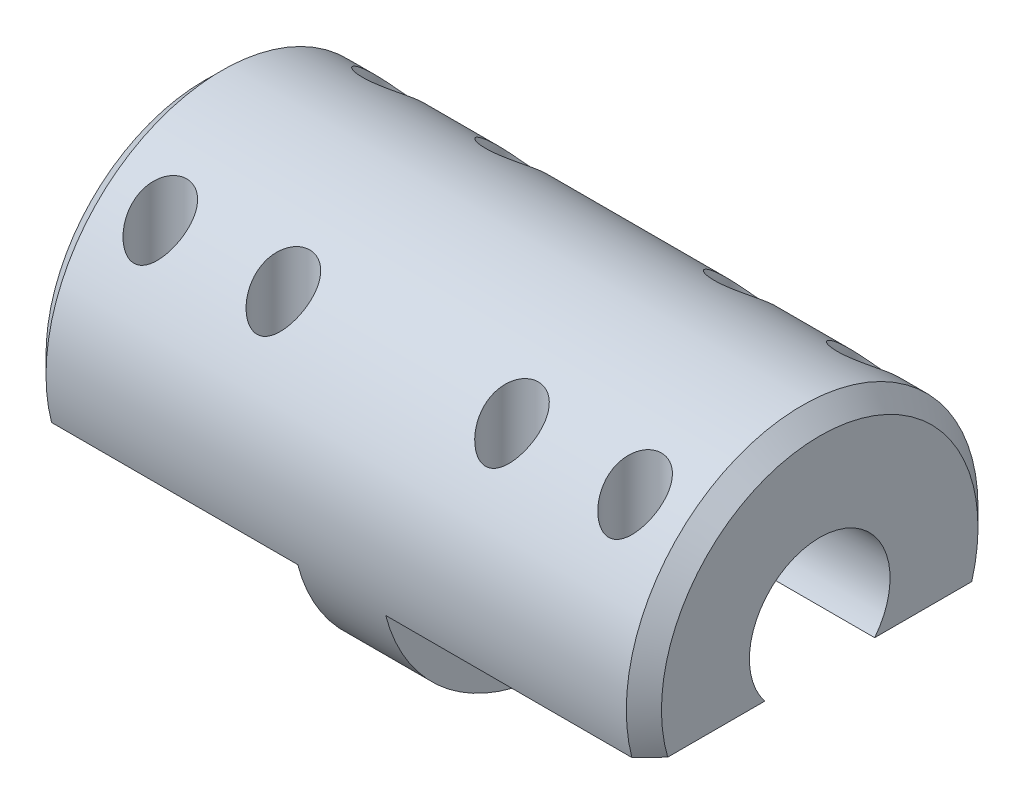
SolidWorks part; units mm, degrees
ref_plane "前视基准面" through (0, 0, 0) normal (0, 0, 1) x (1, 0, 0)
ref_plane "上视基准面" through (0, 0, 0) normal (0, 1, 0) x (1, 0, 0)
ref_plane "右视基准面" through (0, 0, 0) normal (1, 0, 0) x (0, 0, -1)
sketch "草图1" plane through (0, 0, 0) normal (1, 0, 0) x (0, 0, -1)
  circle A0 centre (0, 0) radius 10
  circle A1 centre (0, 0) radius 4
  dimension "D1" = 20
  dimension "D2" = 8
extrude "凸台-拉伸1" add sketch "草图1" along normal blind 35
chamfer "倒角1" distance 1 angle 45 2 edges at (35, 0, -10) (0, 0, -10)
ref_plane "基准面1" through (0, -10, 0) normal (0, -1, 0) x (-1, 0, 0)
sketch "草图3" plane through (0, -10, 0) normal (0, -1, 0) x (-1, 0, 0)
  line L0 (-17.5, 10) -> (-17.5, -10) construction
  line L1 (-1, 10) -> (-34, 10) construction
  line L2 (-34, -10) -> (-1, -10) construction
  line L3 (-7.5, 10) -> (-7.5, 0) construction
  line L4 (-15, 10) -> (0, 10)
  line L5 (-15, 10) -> (-15, -10)
  line L6 (-15, -10) -> (0, -10)
  line L7 (0, 10) -> (0, -10)
  line L8 (-7.5, 0) -> (0, 0) construction
  line L9 (-27.5, 0) -> (-35, 0) construction
  line L10 (-27.5, 10) -> (-27.5, 0) construction
  line L11 (-35, 10) -> (-35, -10)
  line L12 (-20, -10) -> (-35, -10)
  line L13 (-20, 10) -> (-20, -10)
  line L14 (-20, 10) -> (-35, 10)
  circle A0 centre (-4, 6.5) radius 1.5
  circle A1 centre (-11, 6.5) radius 1.5
  circle A2 centre (-11, -6.5) radius 1.5
  circle A3 centre (-4, -6.5) radius 1.5
  circle A4 centre (-31, -6.5) radius 1.5
  circle A5 centre (-24, -6.5) radius 1.5
  circle A6 centre (-24, 6.5) radius 1.5
  circle A7 centre (-31, 6.5) radius 1.5
  dimension "D2" = 3
  dimension "D3" = 4
  dimension "D4" = 13
  dimension "D1" = 15
extrude "切除-拉伸1" cut sketch "草图3" against normal blind 7.5 contours L14 L11 L12 L13 | L4 L7 L6 L5
extrude "切除-拉伸2" cut sketch "草图3<4>" against normal through all contours A7 | A6 | A4 | A5 | A0 | A1 | A2 | A3 region at (4, -10, -6.5) region at (11, -10, -6.5) region at (11, -10, 6.5) region at (4, -10, 6.5) region at (31, -10, 6.5) region at (24, -10, 6.5) region at (24, -10, -6.5) region at (31, -10, -6.5)
sketch "草图3<4>" plane through (0, -10, 0) normal (0, -1, 0) x (-1, 0, 0) same geometry as "草图3"
